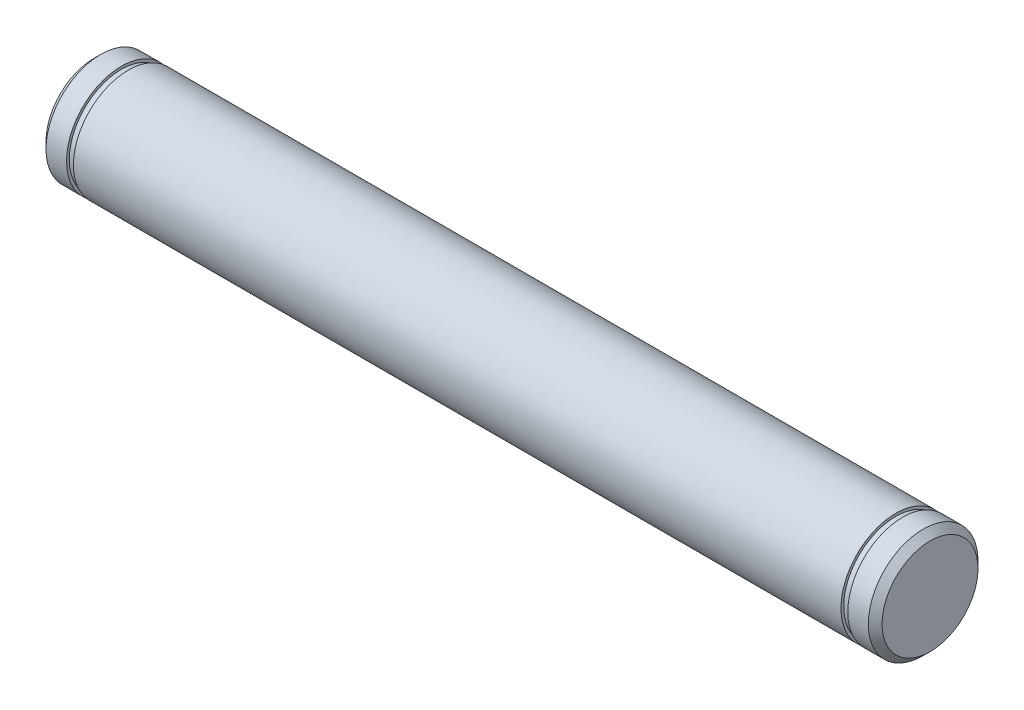
SolidWorks part; units mm, degrees
ref_plane "Front" through (0, 0, 0) normal (0, 0, 1) x (1, 0, 0)
ref_plane "Top" through (0, 0, 0) normal (0, 1, 0) x (1, 0, 0)
ref_plane "Right" through (0, 0, 0) normal (1, 0, 0) x (0, 0, -1)
sketch "Sketch1" plane through (0, 0, 0) normal (1, 0, 0) x (0, 0, -1)
  circle A0 centre (0, 0) radius 2
  dimension "D1" = 4
extrude "Boss-Extrude1" add sketch "Sketch1" along normal blind 30.5
sketch "Sketch2" plane through (30.5, 0, 0) normal (1, 0, 0) x (0, 0, -1)
  circle A0 centre (0, 0) radius 1.9
  circle A1 centre (0, 0) radius 2.4981
  dimension "D1" = 3.8
extrude "Cut-Extrude2" cut sketch "Sketch2" against normal blind 0.25 from offset 1 offset against normal yes
sketch "Sketch3" plane through (0, 0, 0) normal (-1, 0, 0) x (0, 0, 1)
  circle A0 centre (0, 0) radius 1.9
  circle A1 centre (0, 0) radius 2.5
extrude "Cut-Extrude3" cut sketch "Sketch3" against normal blind 0.25 from offset 1 offset against normal yes
chamfer "Chamfer1" distance 0.25 angle 45 2 edges at (0, 0, -2) (30.5, 0, -2)
